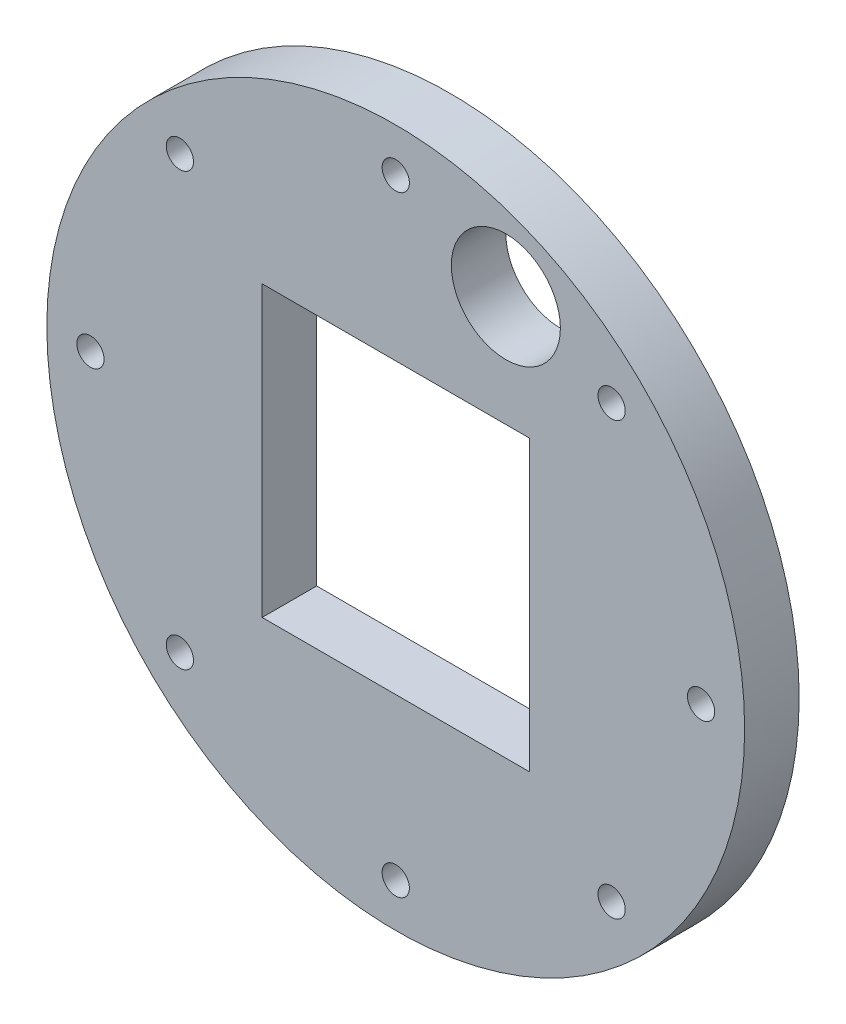
SolidWorks part; units mm, degrees
ref_plane "Alzado" through (0, 0, 0) normal (0, 0, 1) x (1, 0, 0)
ref_plane "Planta" through (0, 0, 0) normal (0, 1, 0) x (1, 0, 0)
ref_plane "Vista lateral" through (0, 0, 0) normal (1, 0, 0) x (0, 0, -1)
sketch "Croquis1" plane through (0, 0, 0) normal (0, 0, 1) x (1, 0, 0)
  circle A0 centre (0, 0) radius 32
  dimension "D1" = 64
extrude "Saliente-Extruir1" add sketch "Croquis1" along normal blind 5
sketch "Croquis2" plane through (0, 0, 5) normal (0, 0, 1) x (1, 0, 0)
  line L0 (0, 0) -> (0, 28) construction
  line L1 (0, 0) -> (19.799, 19.799) construction
  line L2 (0, 0) -> (28, 0) construction
  line L3 (0, 0) -> (19.799, -19.799) construction
  line L4 (0, 0) -> (0, -28) construction
  line L5 (0, 0) -> (-19.799, -19.799) construction
  line L6 (0, 0) -> (-28, 0) construction
  line L7 (0, 0) -> (-19.799, 19.799) construction
  circle A0 centre (0, 28) radius 1.25
  circle A1 centre (0, 0) radius 32 construction
  circle A2 centre (19.799, 19.799) radius 1.25
  circle A3 centre (28, 0) radius 1.25
  circle A4 centre (19.799, -19.799) radius 1.25
  circle A5 centre (0, -28) radius 1.25
  circle A6 centre (-19.799, -19.799) radius 1.25
  circle A7 centre (-28, 0) radius 1.25
  circle A8 centre (-19.799, 19.799) radius 1.25
  point P19 (0, 0)
  dimension "D1" = 2.5
  dimension "D2" = 28
  dimension "D3" = 8
extrude "Cortar-Extruir1" cut sketch "Croquis2" against normal through all
sketch "Croquis3" plane through (0, 0, 5) normal (0, 0, 1) x (1, 0, 0)
  line L0 (0, 32) -> (0, -32) construction
  line L1 (-12.25, -13.25) -> (-12.25, 13.25)
  line L2 (-12.25, -13.25) -> (12.25, -13.25)
  line L3 (12.25, -13.25) -> (12.25, 13.25)
  line L4 (-12.25, 13.25) -> (12.25, 13.25)
  line L5 (-12.25, -13.25) -> (12.25, 13.25) construction
  line L6 (12.25, -13.25) -> (-12.25, 13.25) construction
  circle A0 centre (0, 0) radius 32 construction
  point P0 (0, 0)
  dimension "D1" = 24.5
  dimension "D2" = 26.5
  dimension "D3" = 0
extrude "Cortar-Extruir2" cut sketch "Croquis3" against normal blind 10
sketch "Croquis4" plane through (0, 0, 0) normal (0, 0, -1) x (-1, 0, 0)
  line L0 (-14.1, 15.4) -> (14.4, 15.4) construction
  line L1 (-14.1, -13.1) -> (-14.1, 15.4) construction
  circle A0 centre (-10.1, 23.4) radius 5
  point P2 (-10.3484, 22.0944)
  point P3 (0, 0)
  point P4 (-10.2811, 23.6416)
  dimension "D1" = 10
  dimension "D2" = 8
  dimension "D3" = 4
extrude "Cortar-Extruir3" cut sketch "Croquis4" against normal blind 10
